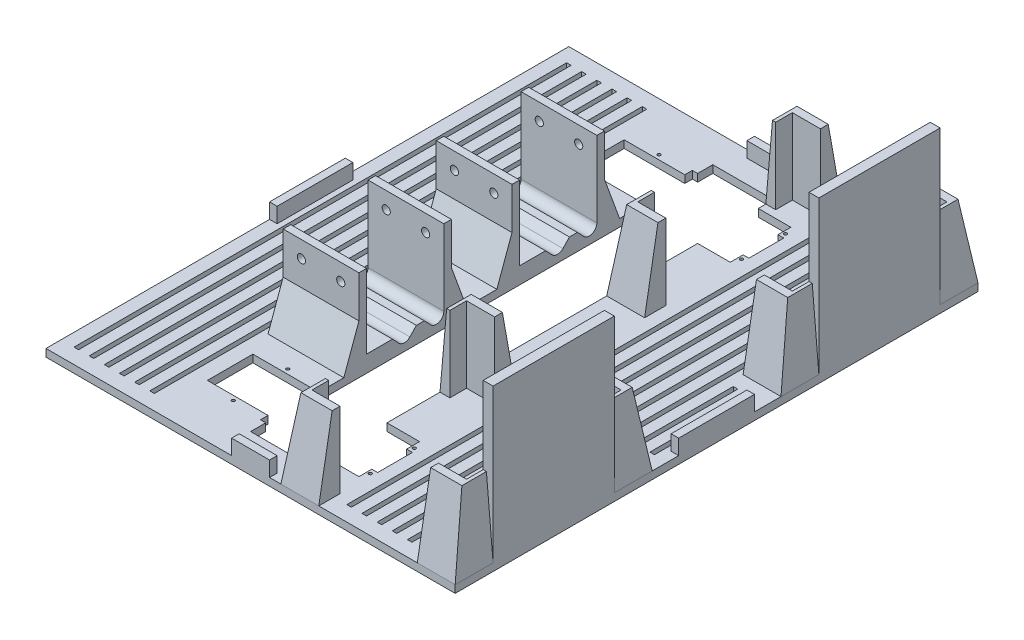
SolidWorks part; units mm, degrees
ref_plane "Front Plane" through (0, 0, 0) normal (0, 0, 1) x (1, 0, 0)
ref_plane "Top Plane" through (0, 0, 0) normal (0, 1, 0) x (1, 0, 0)
ref_plane "Right Plane" through (0, 0, 0) normal (1, 0, 0) x (0, 0, -1)
sketch "Sketch1" plane through (0, 0, 0) normal (0, 1, 0) x (1, 0, 0)
  line L1 (0, 0) -> (115, 0)
  line L2 (0, 0) -> (0, 345)
  line L3 (0, 345) -> (115, 345)
  line L5 (155, 345) -> (270, 345)
  line L7 (155, 0) -> (270, 0)
  line L8 (270, 345) -> (270, 0)
  line L9 (115, 345) -> (155, 345)
  line L11 (115, 325) -> (155, 325)
  line L13 (115, 20) -> (155, 20)
  line L17 (155, 325) -> (155, 20)
  line L18 (115, 20) -> (115, 325)
  line L20 (115, 345) -> (115, 325) construction
  line L21 (115, 20) -> (115, 0) construction
  line L22 (115, 0) -> (155, 0)
  dimension "D1" = 345
  dimension "D2" = 270
  dimension "D3" = 40
  dimension "D4" = 20
  dimension "D5" = 20
extrude "Boss-Extrude1" add sketch "Sketch1" along normal blind 5
sketch "Sketch2" plane through (0, 5, 0) normal (0, 1, 0) x (1, 0, 0)
  line L1 (65, 253.5) -> (115, 253.5)
  line L2 (65, 253.5) -> (65, 248.5)
  line L3 (65, 248.5) -> (115, 248.5)
  line L4 (115, 253.5) -> (115, 248.5)
  line L5 (65, 197.5) -> (115, 197.5)
  line L6 (65, 197.5) -> (65, 192.5)
  line L7 (65, 192.5) -> (115, 192.5)
  line L8 (115, 197.5) -> (115, 192.5)
  line L9 (115, 325) -> (115, 20) construction
  line L10 (0, 172.5) -> (270, 172.5) construction
  line L12 (65, 152.5) -> (115, 152.5)
  line L13 (115, 147.5) -> (115, 152.5)
  line L14 (65, 147.5) -> (115, 147.5)
  line L15 (65, 147.5) -> (65, 152.5)
  line L16 (65, 96.5) -> (115, 96.5)
  line L17 (115, 91.5) -> (115, 96.5)
  line L18 (65, 91.5) -> (115, 91.5)
  line L19 (65, 91.5) -> (65, 96.5)
  line L21 (270, 0) -> (270, 345) construction
  line L22 (0, 345) -> (0, 0) construction
  dimension "D1" = 5
  dimension "D2" = 51
  dimension "D3" = 50
  dimension "D4" = 40
extrude "Boss-Extrude2" add sketch "Sketch2" along normal blind 55
chamfer "Chamfer1" distance 10 angle 70 4 edges at (90, 5, -91.5) (90, 5, -152.5) (90, 5, -192.5) (90, 5, -253.5)
sketch "Sketch4" plane through (115, 0, 0) normal (1, 0, 0) x (0, 0, -1)
  line L0 (147.5, 60) -> (147.5, 5) construction
  line L1 (96.5, 5) -> (147.5, 5)
  line L2 (96.5, 5) -> (96.5, 11)
  line L3 (96.5, 11) -> (147.5, 11)
  line L4 (147.5, 5) -> (147.5, 11)
  line L5 (142.5, 5) -> (142.5, 11) construction
  line L6 (134.601, 11) -> (138.4184, 7.112)
  line L7 (134.601, 11) -> (137.601, 11)
  line L8 (147.5, 10) -> (96.5, 10) construction
  line L9 (125.1038, 6.534) -> (129.399, 11)
  line L10 (129.399, 11) -> (126.399, 11)
  line L11 (117.8962, 6.534) -> (113.601, 11)
  line L12 (113.601, 11) -> (116.601, 11)
  line L13 (172.5, 5) -> (172.5, 54.1934) construction
  line L14 (182.5, 5) -> (162.5, 5) construction
  line L19 (197.5, 5) -> (248.5, 5)
  line L20 (197.5, 5) -> (197.5, 11)
  line L21 (197.5, 11) -> (248.5, 11)
  line L22 (248.5, 5) -> (248.5, 11)
  line L23 (243.5, 5) -> (243.5, 11) construction
  line L24 (235.601, 11) -> (239.8962, 6.534)
  line L25 (235.601, 11) -> (238.601, 11)
  line L26 (248.5, 10) -> (197.5, 10) construction
  line L27 (226.1038, 6.534) -> (230.399, 11)
  line L28 (230.399, 11) -> (227.399, 11)
  line L29 (218.8962, 6.534) -> (214.601, 11)
  line L30 (214.601, 11) -> (217.601, 11)
  line L31 (248.5, 60) -> (248.5, 5) construction
  line L32 (197.5, 60) -> (197.5, 5) construction
  circle A0 centre (142.5, 10) radius 5
  circle A1 centre (121.5, 10) radius 5
  circle A4 centre (243.5, 10) radius 5
  circle A5 centre (222.5, 10) radius 5
  line M10 (248.5, 5) -> (197.5, 5)
  line M11 (197.5, 5) -> (197.5, 60)
  line M20 (147.5, 5) -> (96.5, 5)
  line M21 (96.5, 5) -> (96.5, 60)
  dimension "D2" = 10
  dimension "D5" = 10
  dimension "D10" = 10
  dimension "D16" = 10
  dimension "D1" = 6
  dimension "D3" = 6
  dimension "D4" = 3
  dimension "D6" = 26
  dimension "D7" = 3
  dimension "D8" = 3
  dimension "D9" = 6
  dimension "D11" = 6
  dimension "D12" = 3
  dimension "D13" = 3
  dimension "D14" = 3
  dimension "D15" = 26
extrude "Boss-Extrude3" add sketch "Sketch4" against normal blind 50 contours A1 L11 L3 M21 M20 | A1 L1 A0 L6 L3 L9 | A0 L4 M20 | A5 L29 L21 M11 M10 | A5 L19 A4 L24 L21 L27 | A4 L22 M10
sketch "Sketch3" plane through (0, 0, -248.5) normal (0, 0, 1) x (1, 0, 0)
  line L0 (90, 5) -> (90, 60) construction
  line L1 (65, 5) -> (115, 5) construction
  line L2 (65, 60) -> (115, 60) construction
  line L3 (65, 5) -> (115, 5) construction
  circle A0 centre (77, 49) radius 2.7
  circle A1 centre (103, 49) radius 2.7
  dimension "D3" = 5.4
  dimension "D1" = 13
  dimension "D2" = 44
extrude "Cut-Extrude1" cut sketch "Sketch3" against normal through all both and the other way through all
sketch "Sketch5" plane through (0, 5, 0) normal (0, 1, 0) x (1, 0, 0)
  line L0 (155, 20) -> (155, 325) construction
  line L1 (270, 0) -> (155, 0)
  line L2 (270, 0) -> (270, 130)
  line L3 (270, 130) -> (155, 130)
  line L4 (155, 0) -> (155, 130)
  line L5 (270, 172.5) -> (155, 172.5) construction
  line L6 (161.5, 116) -> (263.5, 116)
  line L7 (161.5, 116) -> (161.5, 14)
  line L8 (161.5, 14) -> (263.5, 14)
  line L9 (263.5, 116) -> (263.5, 14)
  line L10 (270, 0) -> (270, 345) construction
  line L11 (263.5, 229) -> (263.5, 331)
  line L12 (161.5, 331) -> (263.5, 331)
  line L13 (161.5, 229) -> (161.5, 331)
  line L14 (161.5, 229) -> (263.5, 229)
  line L15 (155, 345) -> (155, 215)
  line L16 (270, 215) -> (155, 215)
  line L17 (270, 345) -> (270, 215)
  line L18 (270, 345) -> (155, 345)
  dimension "D1" = 115
  dimension "D2" = 130
  dimension "D3" = 14
  dimension "D4" = 14
  dimension "D5" = 6.5
  dimension "D6" = 6.5
extrude "Boss-Extrude4" add sketch "Sketch5" along normal blind 50
sketch "Sketch6" plane through (0, 0, -345) normal (0, 0, -1) x (-1, 0, 0)
  line L0 (-270, 55) -> (-155, 55) construction
  line L1 (-180, 5) -> (-245, 5)
  line L2 (-180, 5) -> (-180, 55)
  line L3 (-180, 55) -> (-245, 55)
  line L4 (-245, 5) -> (-245, 55)
  line L5 (-155, 55) -> (-155, 5) construction
  line L6 (-270, 55) -> (-270, 0) construction
  dimension "D1" = 25
  dimension "D2" = 25
extrude "Cut-Extrude2" cut sketch "Sketch6" against normal through all and the other way through all
chamfer "Chamfer2" distance 50 angle 10 8 edges at (257.5, 55, -215) (167.5, 55, -215) (167.5, 55, -345) (257.5, 55, -345) (167.5, 55, 0) (257.5, 55, 0) (257.5, 55, -130) (167.5, 55, -130)
chamfer "Chamfer3" distance 50 angle 5 4 edges at (270, 55, -280) (155, 55, -280) (155, 55, -65) (270, 55, -65)
sketch "Sketch7" plane through (0, 5, 0) normal (0, 1, 0) x (1, 0, 0)
  line L0 (270, 130) -> (270, 215) construction
  line L1 (270, 197.5) -> (265, 197.5)
  line L2 (270, 197.5) -> (270, 147.5)
  line L3 (270, 147.5) -> (265, 147.5)
  line L4 (265, 197.5) -> (265, 147.5)
  line L5 (155, 345) -> (0, 345) construction
  line L6 (147.5, 345) -> (122.5, 345)
  line L7 (147.5, 345) -> (147.5, 340)
  line L8 (147.5, 340) -> (122.5, 340)
  line L9 (122.5, 345) -> (122.5, 340)
  line L10 (155, 325) -> (115, 325) construction
  line L11 (155, 172.5) -> (115, 172.5) construction
  line L12 (155, 130) -> (155, 215) construction
  line L13 (115, 182.5) -> (115, 162.5) construction
  line L14 (5, 197.5) -> (5, 147.5)
  line L15 (135, 208.8602) -> (135, 147.5) construction
  line L16 (0, 147.5) -> (5, 147.5)
  line L17 (0, 197.5) -> (0, 147.5)
  line L18 (0, 197.5) -> (5, 197.5)
  line L19 (122.5, 0) -> (122.5, 5)
  line L20 (147.5, 5) -> (122.5, 5)
  line L21 (147.5, 0) -> (147.5, 5)
  line L22 (147.5, 0) -> (122.5, 0)
  point P6 (270, 172.5)
  point P13 (135, 345)
  point P16 (135, 325)
  dimension "D1" = 5
  dimension "D2" = 50
  dimension "D3" = 5
  dimension "D4" = 25
  dimension "D5" = 0
extrude "Boss-Extrude5" add sketch "Sketch7" along normal blind 10
sketch "Sketch8" plane through (270, 0, 0) normal (1, 0, 0) x (0, 0, -1)
  line L0 (130, 5) -> (0, 5) construction
  line L1 (25, 5) -> (105, 5)
  line L2 (25, 5) -> (25, 55)
  line L3 (25, 55) -> (105, 55)
  line L4 (105, 5) -> (105, 55)
  line L5 (8.8163, 55) -> (121.1837, 55) construction
  line L6 (172.5, 15) -> (172.5, 34.1956) construction
  line L7 (147.5, 15) -> (197.5, 15) construction
  line L8 (240, 5) -> (240, 55)
  line L9 (320, 55) -> (240, 55)
  line L10 (320, 5) -> (320, 55)
  line L11 (320, 5) -> (240, 5)
  dimension "D1" = 25
  dimension "D2" = 25
extrude "Cut-Extrude3" cut sketch "Sketch8" against normal blind 132
sketch "Sketch9" plane through (0, 5, 0) normal (0, 1, 0) x (1, 0, 0)
  line L0 (91.5, 68) -> (91.5, 32) construction
  line L2 (178.5, 64.5) -> (178.5, 35.5) construction
  line L3 (178.5, 50) -> (91.5, 50) construction
  line L4 (135, 50) -> (135, 0) construction
  line L5 (122.5, 0) -> (147.5, 0) construction
  line L6 (5, 172.5) -> (227.7216, 172.5) construction
  line L7 (5, 147.5) -> (5, 197.5) construction
  line L9 (111.5, 30) -> (176.5, 30)
  line L11 (111.5, 70) -> (176.5, 70)
  line L13 (71.5, 35) -> (111.5, 35)
  line L14 (71.5, 35) -> (71.5, 65)
  line L15 (71.5, 65) -> (111.5, 65)
  line L17 (176.5, 61.5) -> (180.3212, 61.5)
  line L19 (176.5, 38.5) -> (180.3212, 38.5)
  line L20 (180.3212, 61.5) -> (180.3212, 38.5)
  line L21 (111.5, 70) -> (111.5, 65)
  line L22 (111.5, 35) -> (111.5, 30)
  line L23 (176.5, 70) -> (176.5, 61.5)
  line L24 (176.5, 38.5) -> (176.5, 30)
  line L25 (135, 295) -> (135, 345) construction
  line L26 (178.5, 295) -> (91.5, 295) construction
  line L27 (178.5, 280.5) -> (178.5, 309.5) construction
  line L28 (91.5, 277) -> (91.5, 313) construction
  line L29 (176.5, 306.5) -> (176.5, 315)
  line L30 (176.5, 275) -> (176.5, 283.5)
  line L31 (111.5, 310) -> (111.5, 315)
  line L32 (111.5, 275) -> (111.5, 280)
  line L33 (180.3212, 283.5) -> (180.3212, 306.5)
  line L34 (176.5, 306.5) -> (180.3212, 306.5)
  line L35 (176.5, 283.5) -> (180.3212, 283.5)
  line L36 (71.5, 280) -> (111.5, 280)
  line L37 (71.5, 310) -> (71.5, 280)
  line L38 (71.5, 310) -> (111.5, 310)
  line L39 (111.5, 275) -> (176.5, 275)
  line L40 (111.5, 315) -> (176.5, 315)
  circle A0 centre (91.5, 68) radius 1
  circle A1 centre (91.5, 32) radius 1
  circle A2 centre (178.5, 64.5) radius 1
  circle A3 centre (178.5, 35.5) radius 1
  circle A8 centre (178.5, 309.5) radius 1
  circle A9 centre (178.5, 280.5) radius 1
  circle A10 centre (91.5, 313) radius 1
  circle A11 centre (91.5, 277) radius 1
  point P4 (91.5, 50)
  point P13 (135, 0)
  dimension "D2" = 2
  dimension "D3" = 2
  dimension "D6" = 2
  dimension "D7" = 2
  dimension "D16" = 3
  dimension "D1" = 36
  dimension "D4" = 50
  dimension "D5" = 29
  dimension "D8" = 87
  dimension "D9" = 0
  dimension "D11" = 5
  dimension "D12" = 40
  dimension "D13" = 40
  dimension "D14" = 30
  dimension "D15" = 3
extrude "Cut-Extrude4" cut sketch "Sketch9" against normal through all
sketch "Sketch10" plane through (0, 5, 0) normal (0, 1, 0) x (1, 0, 0)
  line L0 (10, 335) -> (10, 10)
  line L1 (5, 172.5) -> (265, 172.5) construction
  line L2 (5, 147.5) -> (5, 197.5) construction
  line L3 (265, 197.5) -> (265, 147.5) construction
  line L4 (0, 345) -> (0, 197.5) construction
  line L5 (122.5, 345) -> (0, 345) construction
  line L6 (20, 335) -> (20, 10)
  line L7 (30, 335) -> (30, 10)
  line L8 (40, 335) -> (40, 10)
  line L9 (50, 335) -> (50, 10)
  line L10 (60, 335) -> (60, 10)
  line L11 (260, 335) -> (260, 10) construction
  line L13 (245, 345) -> (270, 345) construction
  line L14 (250, 335) -> (250, 10) construction
  line L15 (240, 335) -> (240, 10)
  line L16 (230, 335) -> (230, 10)
  line L17 (220, 335) -> (220, 10)
  line L18 (210, 335) -> (210, 10)
  line L19 (270, 147.5) -> (270, 197.5) construction
  line L20 (200, 335) -> (200, 10)
  line L21 (190, 335) -> (190, 10)
  line L22 (260, 321) -> (260, 239)
  line L23 (263.5, 331) -> (245, 331) construction
  line L24 (245, 229) -> (263.5, 229) construction
  line L26 (260, 205) -> (260, 140)
  line L27 (245, 215) -> (270, 215) construction
  line L28 (270, 130) -> (245, 130) construction
  line L29 (260, 106) -> (260, 24)
  line L30 (263.5, 116) -> (245, 116) construction
  line L31 (245, 14) -> (263.5, 14) construction
  line L32 (250, 321) -> (250, 239)
  line L33 (250, 205) -> (250, 140)
  line L34 (250, 106) -> (250, 24)
  point P8 (10, 172.5)
  point P29 (260, 172.5)
  dimension "D1" = 10
  dimension "D2" = 10
  dimension "D4" = 10
  dimension "D5" = 10
  dimension "D7" = 10
  dimension "D8" = 10
  dimension "D9" = 10
  dimension "D10" = 10
  dimension "D11" = 10
  dimension "D12" = 10
  dimension "D3" = 6
  dimension "D6" = 8
  dimension "D13" = 2
extrude "Cut-Extrude-Thin1" cut sketch "Sketch10" against normal through all thin thin type mid plane wall 3
sketch "Sketch11" plane through (0, 5, 0) normal (0, 1, 0) x (1, 0, 0)
  line L0 (270, 25) -> (270, 105) construction
  line L1 (263.5, 25) -> (270, 25)
  line L2 (263.5, 25) -> (263.5, 105)
  line L3 (263.5, 105) -> (270, 105)
  line L4 (270, 25) -> (270, 105)
  line L5 (263.5, 25) -> (270, 105) construction
  line L6 (263.5, 105) -> (270, 25) construction
  line L7 (263.5, 25) -> (270, 25) construction
  line L9 (263.5, 320) -> (270, 320)
  line L10 (263.5, 320) -> (263.5, 240)
  line L11 (263.5, 240) -> (270, 240)
  line L12 (270, 320) -> (270, 240)
  point P0 (266.75, 65)
extrude "Boss-Extrude6" add sketch "Sketch11" along normal blind 101
